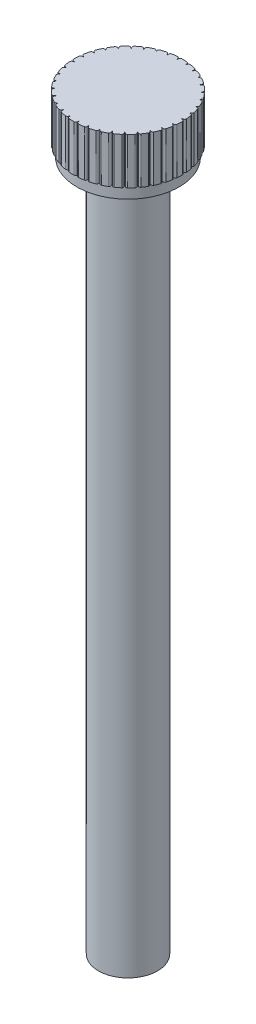
SolidWorks part; units mm, degrees
ref_plane "Plan de face" through (0, 0, 0) normal (0, 0, 1) x (1, 0, 0)
ref_plane "Plan de dessus" through (0, 0, 0) normal (0, 1, 0) x (1, 0, 0)
ref_plane "Plan de droite" through (0, 0, 0) normal (1, 0, 0) x (0, 0, -1)
sketch "Esquisse1" plane through (0, 0, 0) normal (0, 0, 1) x (1, 0, 0)
  line L0 (0, 33.0242) -> (0, -4.925) construction
  line L1 (0, 33.0242) -> (-2.75, 33.0242)
  line L2 (-2.75, 33.0242) -> (-2.75, 30.675)
  line L3 (-2.6, 30.075) -> (-1.5, 30.075)
  line L4 (-1.5, 30.075) -> (-1.5, -4.925)
  line L5 (-1.5, -4.925) -> (0, -4.925)
  line L6 (-2.75, 30.675) -> (-2.6, 30.675)
  line L7 (-2.6, 30.675) -> (-2.6, 30.075)
  line L8 (0, 33.0242) -> (0, -4.925)
  dimension "D1" = 1.5
  dimension "D2" = 35
  dimension "D3" = 2.6
  dimension "D4" = 0.6
  dimension "D5" = 2.75
revolve "Révolution1" add sketch "Esquisse1" angle 360 about L0
sketch "Esquisse2" plane through (0, 33.0242, 0) normal (0, 1, 0) x (1, 0, 0)
  line L0 (0, 0) -> (0, 2.75) construction
  line L1 (0, 0) -> (0.7118, 2.6563) construction
  line L2 (0.3296, 2.6547) -> (0.3394, 2.5778)
  line L3 (0.3394, 2.5778) -> (0.3687, 2.6495)
  line L4 (0.7856, 2.5571) -> (0.7818, 2.4797)
  line L5 (0.3589, 2.7265) -> (0, 0) construction
  line L6 (0.7818, 2.4797) -> (0.8232, 2.5453)
  line L7 (1.2177, 2.3819) -> (1.2005, 2.3062)
  line L8 (1.2005, 2.3062) -> (1.2527, 2.3636)
  line L9 (1.6128, 2.1342) -> (1.5828, 2.0627)
  line L10 (1.5828, 2.0627) -> (1.6441, 2.1102)
  line L11 (1.9589, 1.8218) -> (1.9169, 1.7565)
  line L12 (1.9169, 1.7565) -> (1.9856, 1.7926)
  line L13 (2.2455, 1.4539) -> (2.1928, 1.397)
  line L14 (2.1928, 1.397) -> (2.2667, 1.4206)
  line L15 (2.4638, 1.0419) -> (2.4021, 0.995)
  line L16 (2.4021, 0.995) -> (2.4789, 1.0054)
  line L17 (2.6073, 0.5983) -> (2.5384, 0.5627)
  line L18 (2.5384, 0.5627) -> (2.6159, 0.5597)
  line L19 (2.6716, 0.1364) -> (2.5975, 0.1134)
  line L20 (2.5975, 0.1134) -> (2.6733, 0.097)
  line L21 (2.6547, -0.3296) -> (2.5778, -0.3394)
  line L22 (2.5778, -0.3394) -> (2.6495, -0.3687)
  line L23 (2.5571, -0.7856) -> (2.4797, -0.7818)
  line L24 (2.4797, -0.7818) -> (2.5453, -0.8232)
  line L25 (2.3819, -1.2177) -> (2.3062, -1.2005)
  line L26 (2.3062, -1.2005) -> (2.3636, -1.2527)
  line L27 (2.1342, -1.6128) -> (2.0627, -1.5828)
  line L28 (2.0627, -1.5828) -> (2.1102, -1.6441)
  line L29 (1.8218, -1.9589) -> (1.7565, -1.9169)
  line L30 (1.7565, -1.9169) -> (1.7926, -1.9856)
  line L31 (1.4539, -2.2455) -> (1.397, -2.1928)
  line L32 (1.397, -2.1928) -> (1.4206, -2.2667)
  line L33 (1.0419, -2.4638) -> (0.995, -2.4021)
  line L34 (0.995, -2.4021) -> (1.0054, -2.4789)
  line L35 (0.5983, -2.6073) -> (0.5627, -2.5384)
  line L36 (0.5627, -2.5384) -> (0.5597, -2.6159)
  line L37 (0.1364, -2.6716) -> (0.1134, -2.5975)
  line L38 (0.1134, -2.5975) -> (0.097, -2.6733)
  line L39 (-0.3296, -2.6547) -> (-0.3394, -2.5778)
  line L40 (-0.3394, -2.5778) -> (-0.3687, -2.6495)
  line L41 (-0.7856, -2.5571) -> (-0.7818, -2.4797)
  line L42 (-0.7818, -2.4797) -> (-0.8232, -2.5453)
  line L43 (-1.2177, -2.3819) -> (-1.2005, -2.3062)
  line L44 (-1.2005, -2.3062) -> (-1.2527, -2.3636)
  line L45 (-1.6128, -2.1342) -> (-1.5828, -2.0627)
  line L46 (-1.5828, -2.0627) -> (-1.6441, -2.1102)
  line L47 (-1.9589, -1.8218) -> (-1.9169, -1.7565)
  line L48 (-1.9169, -1.7565) -> (-1.9856, -1.7926)
  line L49 (-2.2455, -1.4539) -> (-2.1928, -1.397)
  line L50 (-2.1928, -1.397) -> (-2.2667, -1.4206)
  line L51 (-2.4638, -1.0419) -> (-2.4021, -0.995)
  line L52 (-2.4021, -0.995) -> (-2.4789, -1.0054)
  line L53 (-2.6073, -0.5983) -> (-2.5384, -0.5627)
  line L54 (-2.5384, -0.5627) -> (-2.6159, -0.5597)
  line L55 (-2.6716, -0.1364) -> (-2.5975, -0.1134)
  line L56 (-2.5975, -0.1134) -> (-2.6733, -0.097)
  line L57 (-2.6547, 0.3296) -> (-2.5778, 0.3394)
  line L58 (-2.5778, 0.3394) -> (-2.6495, 0.3687)
  line L59 (-2.5571, 0.7856) -> (-2.4797, 0.7818)
  line L60 (-2.4797, 0.7818) -> (-2.5453, 0.8232)
  line L61 (-2.3819, 1.2177) -> (-2.3062, 1.2005)
  line L62 (-2.3062, 1.2005) -> (-2.3636, 1.2527)
  line L63 (-2.1342, 1.6128) -> (-2.0627, 1.5828)
  line L64 (-2.0627, 1.5828) -> (-2.1102, 1.6441)
  line L65 (-1.8218, 1.9589) -> (-1.7565, 1.9169)
  line L66 (-1.7565, 1.9169) -> (-1.7926, 1.9856)
  line L67 (-1.4539, 2.2455) -> (-1.397, 2.1928)
  line L68 (-1.397, 2.1928) -> (-1.4206, 2.2667)
  line L69 (-1.0419, 2.4638) -> (-0.995, 2.4021)
  line L70 (-0.995, 2.4021) -> (-1.0054, 2.4789)
  line L71 (-0.5983, 2.6073) -> (-0.5627, 2.5384)
  line L72 (-0.5627, 2.5384) -> (-0.5597, 2.6159)
  line L73 (-0.1364, 2.6716) -> (-0.1134, 2.5975)
  line L74 (-0.1134, 2.5975) -> (-0.097, 2.6733)
  line L75 (0.2089, 2.6706) -> (0.4974, 2.6326) construction
  circle A0 centre (0, 0) radius 2.75 construction
  arc A2 (0.2596, 2.7377) -> (0.4579, 2.7116) centre (0, 0) cw
  arc A5 (0.731, 2.6511) -> (0.9218, 2.5909) centre (0, 0) cw
  arc A6 (0.9218, 2.5909) -> (0.8232, 2.5453) centre (0.9078, 2.4919) ccw
  arc A7 (0.731, 2.6511) -> (0.7856, 2.5571) centre (0.6857, 2.5619) cw
  arc A8 (1.1803, 2.4838) -> (1.3577, 2.3915) centre (0, 0) cw
  arc A9 (1.3577, 2.3915) -> (1.2527, 2.3636) centre (1.3267, 2.2964) ccw
  arc A10 (1.1803, 2.4838) -> (1.2177, 2.3819) centre (1.1201, 2.4039) cw
  arc A11 (1.5937, 2.2412) -> (1.7523, 2.1194) centre (0, 0) cw
  arc A12 (1.7523, 2.1194) -> (1.6441, 2.1102) centre (1.7053, 2.0311) ccw
  arc A13 (1.5937, 2.2412) -> (1.6128, 2.1342) centre (1.5206, 2.1729) cw
  arc A14 (1.9586, 1.9304) -> (2.0937, 1.7829) centre (0, 0) cw
  arc A15 (2.0937, 1.7829) -> (1.9856, 1.7926) centre (2.0321, 1.7041) ccw
  arc A16 (1.9586, 1.9304) -> (1.9589, 1.8218) centre (1.8748, 1.8759) cw
  arc A17 (2.2641, 1.5609) -> (2.3715, 1.3923) centre (0, 0) cw
  arc A18 (2.3715, 1.3923) -> (2.2667, 1.4206) centre (2.2972, 1.3254) ccw
  arc A19 (2.2641, 1.5609) -> (2.2455, 1.4539) centre (2.172, 1.5218) cw
  arc A20 (2.5007, 1.1441) -> (2.5773, 0.9593) centre (0, 0) cw
  arc A21 (2.5773, 0.9593) -> (2.4789, 1.0054) centre (2.4924, 0.9064) ccw
  arc A22 (2.5007, 1.1441) -> (2.4638, 1.0419) centre (2.4033, 1.1215) cw
  arc A23 (2.6614, 0.6924) -> (2.7047, 0.4972) centre (0, 0) cw
  arc A24 (2.7047, 0.4972) -> (2.6159, 0.5597) centre (2.6119, 0.4598) ccw
  arc A25 (2.6614, 0.6924) -> (2.6073, 0.5983) centre (2.5615, 0.6872) cw
  arc A26 (2.7412, 0.2198) -> (2.7499, 0.02) centre (0, 0) cw
  arc A27 (2.7499, 0.02) -> (2.6733, 0.097) centre (2.6521, -0.0008) ccw
  arc A28 (2.7412, 0.2198) -> (2.6716, 0.1364) centre (2.6419, 0.2319) cw
  arc A29 (2.7377, -0.2596) -> (2.7116, -0.4579) centre (0, 0) cw
  arc A30 (2.7116, -0.4579) -> (2.6495, -0.3687) centre (2.6117, -0.4613) ccw
  arc A31 (2.7377, -0.2596) -> (2.6547, -0.3296) centre (2.6421, -0.2304) cw
  arc A32 (2.6511, -0.731) -> (2.5909, -0.9218) centre (0, 0) cw
  arc A33 (2.5909, -0.9218) -> (2.5453, -0.8232) centre (2.4919, -0.9078) ccw
  arc A34 (2.6511, -0.731) -> (2.5571, -0.7856) centre (2.5619, -0.6857) cw
  arc A35 (2.4838, -1.1803) -> (2.3915, -1.3577) centre (0, 0) cw
  arc A36 (2.3915, -1.3577) -> (2.3636, -1.2527) centre (2.2964, -1.3267) ccw
  arc A37 (2.4838, -1.1803) -> (2.3819, -1.2177) centre (2.4039, -1.1201) cw
  arc A38 (2.2412, -1.5937) -> (2.1194, -1.7523) centre (0, 0) cw
  arc A39 (2.1194, -1.7523) -> (2.1102, -1.6441) centre (2.0311, -1.7053) ccw
  arc A40 (2.2412, -1.5937) -> (2.1342, -1.6128) centre (2.1729, -1.5206) cw
  arc A41 (1.9304, -1.9586) -> (1.7829, -2.0937) centre (0, 0) cw
  arc A42 (1.7829, -2.0937) -> (1.7926, -1.9856) centre (1.7041, -2.0321) ccw
  arc A43 (1.9304, -1.9586) -> (1.8218, -1.9589) centre (1.8759, -1.8748) cw
  arc A44 (1.5609, -2.2641) -> (1.3923, -2.3715) centre (0, 0) cw
  arc A45 (1.3923, -2.3715) -> (1.4206, -2.2667) centre (1.3254, -2.2972) ccw
  arc A46 (1.5609, -2.2641) -> (1.4539, -2.2455) centre (1.5218, -2.172) cw
  arc A47 (1.1441, -2.5007) -> (0.9593, -2.5773) centre (0, 0) cw
  arc A48 (0.9593, -2.5773) -> (1.0054, -2.4789) centre (0.9064, -2.4924) ccw
  arc A49 (1.1441, -2.5007) -> (1.0419, -2.4638) centre (1.1215, -2.4033) cw
  arc A50 (0.6924, -2.6614) -> (0.4972, -2.7047) centre (0, 0) cw
  arc A51 (0.4972, -2.7047) -> (0.5597, -2.6159) centre (0.4598, -2.6119) ccw
  arc A52 (0.6924, -2.6614) -> (0.5983, -2.6073) centre (0.6872, -2.5615) cw
  arc A53 (0.2198, -2.7412) -> (0.02, -2.7499) centre (0, 0) cw
  arc A54 (0.02, -2.7499) -> (0.097, -2.6733) centre (-0.0008, -2.6521) ccw
  arc A55 (0.2198, -2.7412) -> (0.1364, -2.6716) centre (0.2319, -2.6419) cw
  arc A56 (-0.2596, -2.7377) -> (-0.4579, -2.7116) centre (0, 0) cw
  arc A57 (-0.4579, -2.7116) -> (-0.3687, -2.6495) centre (-0.4613, -2.6117) ccw
  arc A58 (-0.2596, -2.7377) -> (-0.3296, -2.6547) centre (-0.2304, -2.6421) cw
  arc A59 (-0.731, -2.6511) -> (-0.9218, -2.5909) centre (0, 0) cw
  arc A60 (-0.9218, -2.5909) -> (-0.8232, -2.5453) centre (-0.9078, -2.4919) ccw
  arc A61 (-0.731, -2.6511) -> (-0.7856, -2.5571) centre (-0.6857, -2.5619) cw
  arc A62 (-1.1803, -2.4838) -> (-1.3577, -2.3915) centre (0, 0) cw
  arc A63 (-1.3577, -2.3915) -> (-1.2527, -2.3636) centre (-1.3267, -2.2964) ccw
  arc A64 (-1.1803, -2.4838) -> (-1.2177, -2.3819) centre (-1.1201, -2.4039) cw
  arc A65 (-1.5937, -2.2412) -> (-1.7523, -2.1194) centre (0, 0) cw
  arc A66 (-1.7523, -2.1194) -> (-1.6441, -2.1102) centre (-1.7053, -2.0311) ccw
  arc A67 (-1.5937, -2.2412) -> (-1.6128, -2.1342) centre (-1.5206, -2.1729) cw
  arc A68 (-1.9586, -1.9304) -> (-2.0937, -1.7829) centre (0, 0) cw
  arc A69 (-2.0937, -1.7829) -> (-1.9856, -1.7926) centre (-2.0321, -1.7041) ccw
  arc A70 (-1.9586, -1.9304) -> (-1.9589, -1.8218) centre (-1.8748, -1.8759) cw
  arc A71 (-2.2641, -1.5609) -> (-2.3715, -1.3923) centre (0, 0) cw
  arc A72 (-2.3715, -1.3923) -> (-2.2667, -1.4206) centre (-2.2972, -1.3254) ccw
  arc A73 (-2.2641, -1.5609) -> (-2.2455, -1.4539) centre (-2.172, -1.5218) cw
  arc A74 (-2.5007, -1.1441) -> (-2.5773, -0.9593) centre (0, 0) cw
  arc A75 (-2.5773, -0.9593) -> (-2.4789, -1.0054) centre (-2.4924, -0.9064) ccw
  arc A76 (-2.5007, -1.1441) -> (-2.4638, -1.0419) centre (-2.4033, -1.1215) cw
  arc A77 (-2.6614, -0.6924) -> (-2.7047, -0.4972) centre (0, 0) cw
  arc A78 (-2.7047, -0.4972) -> (-2.6159, -0.5597) centre (-2.6119, -0.4598) ccw
  arc A79 (-2.6614, -0.6924) -> (-2.6073, -0.5983) centre (-2.5615, -0.6872) cw
  arc A80 (-2.7412, -0.2198) -> (-2.7499, -0.02) centre (0, 0) cw
  arc A81 (-2.7499, -0.02) -> (-2.6733, -0.097) centre (-2.6521, 0.0008) ccw
  arc A82 (-2.7412, -0.2198) -> (-2.6716, -0.1364) centre (-2.6419, -0.2319) cw
  arc A83 (-2.7377, 0.2596) -> (-2.7116, 0.4579) centre (0, 0) cw
  arc A84 (-2.7116, 0.4579) -> (-2.6495, 0.3687) centre (-2.6117, 0.4613) ccw
  arc A85 (-2.7377, 0.2596) -> (-2.6547, 0.3296) centre (-2.6421, 0.2304) cw
  arc A86 (-2.6511, 0.731) -> (-2.5909, 0.9218) centre (0, 0) cw
  arc A87 (-2.5909, 0.9218) -> (-2.5453, 0.8232) centre (-2.4919, 0.9078) ccw
  arc A88 (-2.6511, 0.731) -> (-2.5571, 0.7856) centre (-2.5619, 0.6857) cw
  arc A89 (-2.4838, 1.1803) -> (-2.3915, 1.3577) centre (0, 0) cw
  arc A90 (-2.3915, 1.3577) -> (-2.3636, 1.2527) centre (-2.2964, 1.3267) ccw
  arc A91 (-2.4838, 1.1803) -> (-2.3819, 1.2177) centre (-2.4039, 1.1201) cw
  arc A92 (-2.2412, 1.5937) -> (-2.1194, 1.7523) centre (0, 0) cw
  arc A93 (-2.1194, 1.7523) -> (-2.1102, 1.6441) centre (-2.0311, 1.7053) ccw
  arc A94 (-2.2412, 1.5937) -> (-2.1342, 1.6128) centre (-2.1729, 1.5206) cw
  arc A95 (-1.9304, 1.9586) -> (-1.7829, 2.0937) centre (0, 0) cw
  arc A96 (-1.7829, 2.0937) -> (-1.7926, 1.9856) centre (-1.7041, 2.0321) ccw
  arc A97 (-1.9304, 1.9586) -> (-1.8218, 1.9589) centre (-1.8759, 1.8748) cw
  arc A98 (-1.5609, 2.2641) -> (-1.3923, 2.3715) centre (0, 0) cw
  arc A99 (-1.3923, 2.3715) -> (-1.4206, 2.2667) centre (-1.3254, 2.2972) ccw
  arc A100 (-1.5609, 2.2641) -> (-1.4539, 2.2455) centre (-1.5218, 2.172) cw
  arc A101 (-1.1441, 2.5007) -> (-0.9593, 2.5773) centre (0, 0) cw
  arc A102 (-0.9593, 2.5773) -> (-1.0054, 2.4789) centre (-0.9064, 2.4924) ccw
  arc A103 (-1.1441, 2.5007) -> (-1.0419, 2.4638) centre (-1.1215, 2.4033) cw
  arc A104 (-0.6924, 2.6614) -> (-0.4972, 2.7047) centre (0, 0) cw
  arc A105 (-0.4972, 2.7047) -> (-0.5597, 2.6159) centre (-0.4598, 2.6119) ccw
  arc A106 (-0.6924, 2.6614) -> (-0.5983, 2.6073) centre (-0.6872, 2.5615) cw
  arc A107 (-0.2198, 2.7412) -> (-0.02, 2.7499) centre (0, 0) cw
  arc A108 (-0.02, 2.7499) -> (-0.097, 2.6733) centre (0.0008, 2.6521) ccw
  arc A109 (-0.2198, 2.7412) -> (-0.1364, 2.6716) centre (-0.2319, 2.6419) cw
  arc A110 (0.3687, 2.6495) -> (0.4579, 2.7116) centre (0.4613, 2.6117) cw
  arc A111 (0.2596, 2.7377) -> (0.3296, 2.6547) centre (0.2304, 2.6421) cw
  point P14 (0.4972, 2.6311)
  point P263 (0, 0)
  point P264 (0.2094, 2.6741)
  point P265 (0, 0)
  dimension "D2" = 0.2
  dimension "D5" = 0.1
  dimension "D6" = 0.075
  dimension "D7" = 0.1
  dimension "D1" = 15
  dimension "D3" = 2.75
  dimension "D4" = 0.15
  dimension "D8" = 7.5
  dimension "D9" = 36
extrude "Enlèv. mat.-Extru.2" cut sketch "Esquisse2" against normal blind 10
